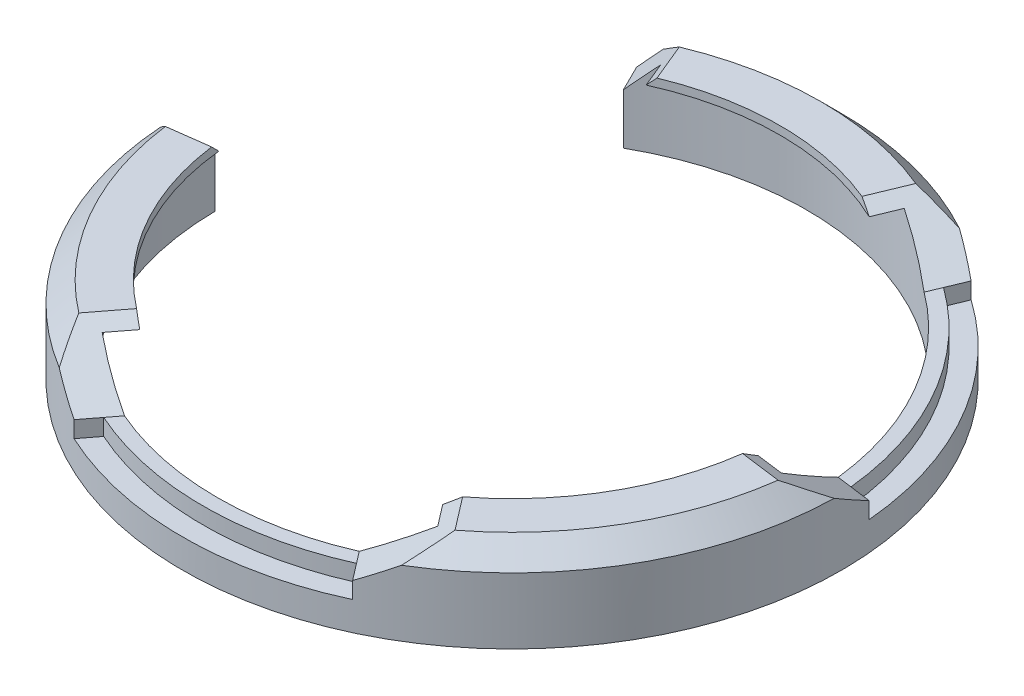
SolidWorks part; units mm, degrees
ref_plane "前视基准面" through (0, 0, 0) normal (0, 0, 1) x (1, 0, 0)
ref_plane "上视基准面" through (0, 0, 0) normal (0, 1, 0) x (1, 0, 0)
ref_plane "右视基准面" through (0, 0, 0) normal (1, 0, 0) x (0, 0, -1)
sketch "草图1" plane through (0, 0, 0) normal (0, 1, 0) x (1, 0, 0)
  circle A0 centre (0, 0) radius 71.5
  circle A1 centre (0, 0) radius 80
  dimension "D1" = 143
  dimension "D2" = 160
extrude "凸台-拉伸1" add sketch "草图1" along normal blind 19
sketch "草图2" plane through (0, 19, 0) normal (0, 1, 0) x (1, 0, 0)
  circle A0 centre (0, 0) radius 71.5
  circle A1 centre (0, 0) radius 71.5 construction
  circle A3 centre (0, 0) radius 65
  circle A4 centre (0, 0) radius 80
  circle A5 centre (0, 0) radius 80 construction
  circle M3 centre (0, 0) radius 80
  circle M4 centre (0, 0) radius 71.5
  dimension "D1" = 130
extrude "凸台-拉伸2" add sketch "草图2" along normal blind 2 contours A3 M4 | M3 M4
sketch "草图3" plane through (0, 21, 0) normal (0, 1, 0) x (1, 0, 0)
  line L0 (0, 0) -> (30.6147, 73.9104)
  line L1 (0, 0) -> (-30.6147, 73.9104)
  line L2 (0, 0) -> (0, 102.3748) construction
  line L3 (0, 0) -> (79.3156, -10.4421)
  line L4 (0, 0) -> (48.7009, -63.4683)
  line L5 (0, 0) -> (-48.7009, -63.4683)
  line L6 (0, 0) -> (-79.3156, -10.4421)
  circle A0 centre (0, 0) radius 80 construction
  circle A1 centre (0, 0) radius 65 construction
  circle A2 centre (0, 0) radius 65
  circle A3 centre (0, 0) radius 80
  point P18 (0, 0)
  circle M6 centre (0, 0) radius 65
  circle M7 centre (0, 0) radius 80
  dimension "D1" = 45
  dimension "D2" = 3
extrude "切除-拉伸1" cut sketch "草图3" against normal blind 10 contours L3 L0 M6 M7 | L6 L1 M6 M7 | L5 L4 M6 M7
chamfer "倒角1" distance 10 angle 60 4 edges at (-46.1137, 11, 60.0965) (46.1137, 11, 60.0965) (75.1019, 11, 9.8874) (28.9883, 11, -69.9839)
chamfer "倒角2" distance 5 angle 45 5 edges at (69.282, 21, 40) (0, 21, -80) (-69.282, 21, 40) (38.4815, 15.9701, -70.1368) (41.4995, 15.9701, 68.3944)
sketch "草图4" plane through (0, 11, 0) normal (0, 1, 0) x (1, 0, 0)
  line L2 (45.8906, 65.529) -> (42.549, 57.4616)
  line L3 (71.0377, 8.1177) -> (79.6951, 6.9779)
  line L4 (45.8906, 65.529) -> (42.549, 57.4616)
  line L5 (71.0377, 8.1177) -> (79.6951, 6.9779)
  line L6 (-28.4887, -65.5793) -> (-33.8045, -72.5069)
  line L7 (33.8045, -72.5069) -> (28.4887, -65.5793)
  line L8 (-28.4887, -65.5793) -> (-33.8045, -72.5069)
  line L9 (33.8045, -72.5069) -> (28.4887, -65.5793)
  circle A0 centre (0, 0) radius 75
  arc A1 (28.7013, 69.291) -> (-28.7013, 69.291) centre (0, 0) ccw construction
  arc A4 (79.6951, 6.9779) -> (45.8906, 65.529) centre (0, 0) ccw
  arc A5 (71.0377, 8.1177) -> (42.549, 57.4616) centre (0, 0) ccw
  arc A6 (79.6951, 6.9779) -> (45.8906, 65.529) centre (0, 0) ccw
  arc A7 (71.0377, 8.1177) -> (42.549, 57.4616) centre (0, 0) ccw
  arc A8 (-28.4887, -65.5793) -> (28.4887, -65.5793) centre (0, 0) ccw
  arc A9 (-33.8045, -72.5069) -> (33.8045, -72.5069) centre (0, 0) ccw
  arc A10 (-28.4887, -65.5793) -> (28.4887, -65.5793) centre (0, 0) ccw
  arc A11 (-33.8045, -72.5069) -> (33.8045, -72.5069) centre (0, 0) ccw
  arc M10 (79.6951, 6.9779) -> (45.8906, 65.529) centre (0, 0) ccw
  line M11 (45.8906, 65.529) -> (42.549, 57.4616)
  dimension "D1" = 0
  dimension "D2" = 0
extrude "切除-拉伸2" cut sketch "草图4" against normal blind 4 contours L8 A11 L9 A0 | A0 L5 M10 M11
sketch "草图7" plane through (0, 11, 0) normal (0, 1, 0) x (1, 0, 0)
  line L0 (-69.282, 40) -> (0, 0) construction
  line L1 (-79.997, -0.6981) -> (0, 0)
  line L2 (0, 0) -> (-39.3939, 69.6285)
  line L5 (-27.3619, 66.0574) -> (-30.6147, 73.9104)
  line L6 (-79.3156, -10.4421) -> (-70.8883, -9.3326)
  arc A0 (-30.6147, 73.9104) -> (-79.3156, -10.4421) centre (0, 0) ccw construction
  arc A3 (-30.6147, 73.9104) -> (-79.3156, -10.4421) centre (0, 0) ccw
  arc A4 (-27.3619, 66.0574) -> (-70.8883, -9.3326) centre (0, 0) ccw
  arc A5 (-39.3939, 69.6285) -> (-79.997, -0.6981) centre (0, 0) ccw
  arc A6 (-35.2083, 62.2304) -> (-71.4973, -0.6239) centre (0, 0) ccw
  arc M9 (-30.6147, 73.9104) -> (-79.3156, -10.4421) centre (0, 0) ccw
  arc M11 (-70.8883, -9.3326) -> (-27.3619, 66.0574) centre (0, 0) cw
  dimension "D1" = 61
  dimension "D2" = 0
extrude "切除-拉伸3" cut sketch "草图7" against normal blind 34 contours L0 A6 L2 M9 | L0 A5 L1 M11
chamfer "倒角3" distance 10 angle 45 2 edges at (-28.9883, 11, -69.9839) (-75.1019, 11, 9.8874)
